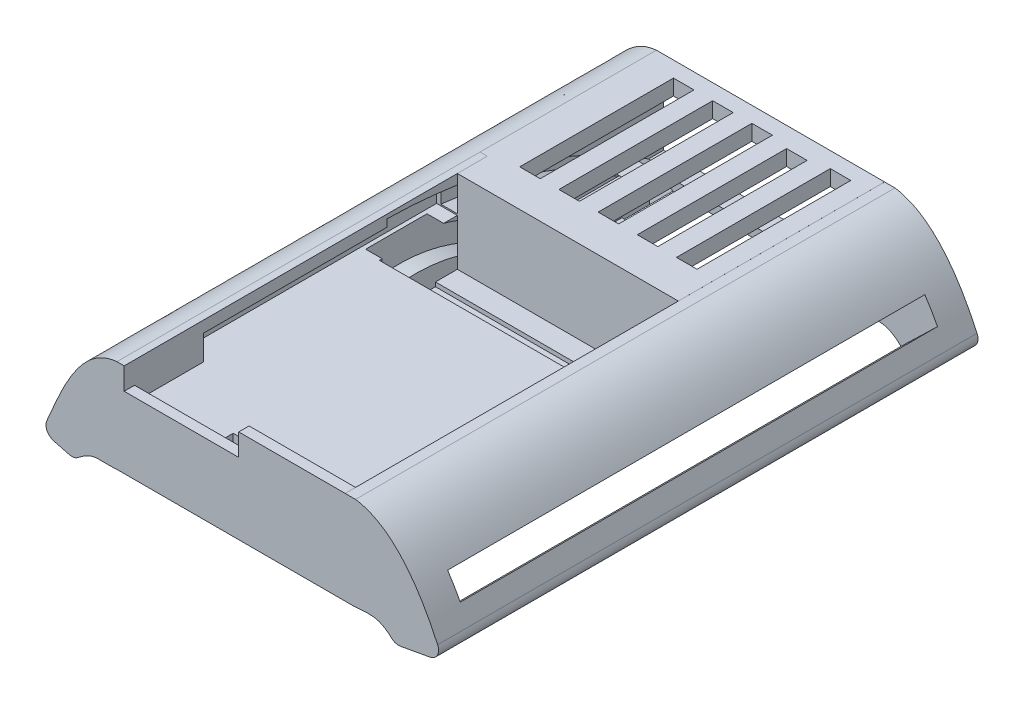
SolidWorks part; units mm, degrees
ref_plane "Front Plane" through (0, 0, 0) normal (0, 0, 1) x (1, 0, 0)
ref_plane "Top Plane" through (0, 0, 0) normal (0, 1, 0) x (1, 0, 0)
ref_plane "Right Plane" through (0, 0, 0) normal (1, 0, 0) x (0, 0, -1)
sketch "Sketch1" plane through (0, 0, 0) normal (0, 0, 1) x (1, 0, 0)
  line L0 (-4.067, -1.1908) -> (-7.2404, -0.3546)
  line L5 (0, 0) -> (22.8691, 0)
  line L9 (23.0423, 8.9983) -> (22.0423, 8.9983)
  line L10 (22.0423, 8.9983) -> (22.0423, 1)
  line L11 (22.0423, 1) -> (0.7423, 1)
  line L12 (0.7423, 1) -> (0.7423, 8.9983)
  line L13 (0.7423, 8.9983) -> (0.0423, 8.9983)
  line L14 (31.4678, -0.3546) -> (26.8755, -1.1908)
  spline S0 degree 3 poles (0.0423, 8.9983) (-4.2131, 8.6488) (-5.9624, 1.8146) (-7.2404, -0.3546) knots 0 0 0 0 1 1 1 1
  spline S1 degree 3 poles (0, 0) (-1.8708, -0.1637) (-2.2399, 0.4307) (-4.067, -1.1908) knots 0 0 0 0 1 1 1 1
  spline S2 degree 2 poles (23.0423, 8.9983) (27.8524, 8.2713) (31.4678, -0.3546) knots 0 0 0 1 1 1
  spline S3 degree 3 poles (22.8691, 0) (24.5642, 0.0744) (25.2973, 0.4291) (26.8755, -1.1908) knots 0 0 0 0 1 1 1 1
  point P13 (0, 0)
  point P14 (0, 0)
  point P15 (22.0587, 5.9972)
  point P16 (0, 0)
  point P17 (0, 0)
  point P18 (0, 0)
  point P19 (26.8687, -1.1908)
  point P20 (31.4678, -0.3546)
  point P21 (0, 0)
  dimension "D3" = 1
  dimension "D1" = 23
  dimension "D2" = 9
  dimension "D4" = 0.7
  dimension "D5" = 1
extrude "Boss-Extrude2" add sketch "Sketch1" along normal blind 52
fillet "Fillet2" radius 1 2 edges at (-4.067, -1.1908, 26) (-7.2404, -0.3546, 26)
ref_plane "Plane10" through (-4.3809, 3.5692, 0) normal (-0.7753, 0.6316, 0) x (0.6316, 0.7753, 0)
sketch "Sketch10" plane through (-4.3809, 3.5692, 0) normal (-0.7753, 0.6316, 0) x (0.6316, 0.7753, 0)
  line L0 (7.0029, 0) -> (-3.689, 0) construction
  line L1 (-3.0069, -50) -> (-0.6561, -50)
  line L2 (-3.0069, -50) -> (-3.0069, -4)
  line L3 (-3.0069, -4) -> (-0.6561, -4)
  line L4 (-0.6561, -50) -> (-0.6561, -4)
  point P4 (-1.8315, -4)
  dimension "D1" = 46
  dimension "D2" = 4
extrude "Cut-Extrude2" cut sketch "Sketch10" against normal blind 6 and the other way blind 3
sketch "Sketch11" plane through (0, 1, 0) normal (0, 1, 0) x (1, 0, 0)
  line L0 (22.0423, 0) -> (0.7423, 0) construction
  line L1 (3.6147, -2) -> (20.6147, -2)
  line L2 (3.6147, -2) -> (3.6147, -17)
  line L3 (3.6147, -17) -> (20.6147, -17)
  line L4 (20.6147, -2) -> (20.6147, -17)
  dimension "D1" = 17
  dimension "D2" = 15
  dimension "D3" = 2
extrude "Peltier" cut sketch "Sketch11" against normal blind 10
sketch "Sketch12" plane through (0, 1, 0) normal (0, 1, 0) x (1, 0, 0)
  line L0 (0.7423, -52) -> (0.7423, 0) construction
  line L1 (0.7423, -22) -> (21.7423, -22)
  line L2 (0.7423, -22) -> (0.7423, -51)
  line L3 (0.7423, -51) -> (21.7423, -51)
  line L4 (21.7423, -22) -> (21.7423, -51)
  line L5 (22.0423, -52) -> (0.7423, -52) construction
  point P4 (21.6862, -25.0592)
  point P5 (0.7604, -25.0044)
  point P6 (1.0987, -24.9782)
  point P7 (2.098, -25.2677)
  point P8 (7.0243, -24.6526)
  point P11 (21.7604, -21.5854)
  dimension "D1" = 29
  dimension "D2" = 21
  dimension "D3" = 1
extrude "Battery" cut sketch "Sketch12" against normal blind 0.4
sketch "Sketch14" plane through (0, 1, 0) normal (0, 1, 0) x (1, 0, 0)
  line L1 (22.0423, -52) -> (0.7423, -52)
  line L2 (22.0423, -52) -> (22.0423, -51)
  line L3 (22.0423, -51) -> (0.7423, -51)
  line L4 (0.7423, -52) -> (0.7423, -51)
extrude "Boss-Extrude4" add sketch "Sketch14" along normal blind 7.9999
sketch "Sketch15" plane through (3.6147, 0, 0) normal (1, 0, 0) x (0, 0, -1)
  line L0 (-2, 1) -> (-17, 1) construction
  line L1 (-17, 0.3705) -> (-13.7023, 0.3705)
  line L2 (-17, 0.3705) -> (-17, 1)
  line L3 (-17, 1) -> (-13.7023, 1)
  line L4 (-13.7023, 0.3705) -> (-13.7023, 1)
  point P7 (0, 0)
  point P8 (-13.7023, 0.3705)
  point P9 (-17, 1)
extrude "Cut-Extrude5" cut sketch "Sketch15" against normal blind 3.6
sketch "Sketch16" plane through (3.6147, 0, 0) normal (1, 0, 0) x (0, 0, -1)
  line L0 (-2, 1) -> (-13.7023, 1) construction
  line L1 (-1.4649, 0.3306) -> (-4.2604, 0.3306)
  line L2 (-1.4649, 0.3306) -> (-1.4649, 1)
  line L3 (-1.4649, 1) -> (-4.2604, 1)
  line L4 (-4.2604, 0.3306) -> (-4.2604, 1)
  point P7 (-4.2604, 0.3306)
extrude "Cut-Extrude6" cut sketch "Sketch16" against normal blind 4.337
fillet "Fillet3" radius 1 2 edges at (3.6147, 0.3306, 3.1302) (3.6147, 0.3705, 15.3511)
sketch "Sketch17" plane through (0.7423, 0, 0) normal (1, 0, 0) x (0, 0, -1)
  line L0 (-26.6799, 8.6073) -> (-26.6799, 5.8973)
  line L1 (-4.2604, 1) -> (-1.4649, 1)
  spline S0 degree 2 poles (-1.4649, 1) (-12.8352, 8.3747) (-26.6799, 8.6073) knots 0 0 0 1 1 1
  spline S1 degree 2 poles (-4.2604, 1) (-14.8676, 6.2725) (-26.6799, 5.8973) knots 0 0 0 1 1 1
  point P5 (0, 0)
  point P8 (0, 0)
  point P9 (-26.6799, 8.6073)
  point P11 (-9.9454, 5.3736)
  point P12 (-17.0967, 4.2862)
  point P13 (-26.6799, 5.8973)
  point P14 (-15.6003, 4.9526)
extrude "Cut-Extrude7" cut sketch "Sketch17" against normal blind 1.6
sketch "Sketch18" plane through (0.7423, 0, 0) normal (1, 0, 0) x (0, 0, -1)
  line L0 (-27.1273, 2.3332) -> (-27.1273, 5.8811)
  line L1 (-17, 1) -> (-13.7023, 1)
  parabola Q0 (-26.6799, 5.8973) -> (-4.2604, 1) focus (-20.1418, -17.3883) apex (-15.3845, 4.9071) construction
  parabola Q1 (-26.6799, 5.8973) -> (-4.2604, 1) focus (-20.1418, -17.3883) apex (-15.3845, 4.9071) construction
  spline S0 degree 2 poles (-13.7023, 1) (-19.5982, 6.7985) (-27.1273, 5.8811) knots 0 0 0 1 1 1
  spline S1 degree 2 poles (-17, 1) (-21.9026, 3.3817) (-27.1273, 2.3332) knots 0 0 0 1 1 1
extrude "Cut-Extrude8" cut sketch "Sketch18" against normal blind 1.6
fillet "Fillet4" radius 1 1 edges at (26.8755, -1.1908, 26)
fillet "Fillet5" radius 1 1 edges at (31.4678, -0.3546, 26)
sketch "Sketch19" plane through (0, 0, 51) normal (0, 0, -1) x (-1, 0, 0)
  line L0 (-0.7423, 0.6) -> (-0.7423, 8.9983) construction
  line L1 (-0.7423, 4.5) -> (-22.0423, 4.5)
  line L2 (-0.7423, 4.5) -> (-0.7423, 5.5)
  line L3 (-0.7423, 5.5) -> (-22.0423, 5.5)
  line L4 (-22.0423, 4.5) -> (-22.0423, 5.5)
  line L5 (-22.0423, 8.9983) -> (-22.0423, 1) construction
  line L6 (-0.7423, 0.6) -> (-21.7423, 0.6) construction
  dimension "D1" = 1
  dimension "D2" = 3.9
extrude "Boss-Extrude5" add sketch "Sketch19" along normal blind 23.6
sketch "Sketch20" plane through (0, 5.5, 0) normal (0, 1, 0) x (1, 0, 0)
  line L0 (0.7423, -51) -> (22.0423, -51) construction
  line L1 (15.7498, -51) -> (8.1239, -51)
  line L2 (15.7498, -51) -> (15.7498, -48.879)
  line L3 (15.7498, -48.879) -> (8.1239, -48.879)
  line L4 (8.1239, -51) -> (8.1239, -48.879)
extrude "Cut-Extrude9" cut sketch "Sketch20" against normal blind 2.6
sketch "Sketch21" plane through (0, 1, 0) normal (0, 1, 0) x (1, 0, 0)
  line L0 (22.0423, -51) -> (22.0423, 0) construction
  line L1 (22.0423, -17) -> (0.7423, -17)
  line L2 (22.0423, -17) -> (22.0423, -19.8861)
  line L3 (22.0423, -19.8861) -> (0.7423, -19.8861)
  line L4 (0.7423, -17) -> (0.7423, -19.8861)
  line L5 (0.7423, -22) -> (0.7423, -17) construction
extrude "Boss-Extrude6" add sketch "Sketch21" along normal blind 8
sketch "Sketch22" plane through (22.0423, 0, 0) normal (-1, 0, 0) x (0, 0, 1)
  line L0 (0, 8.9983) -> (0, 1) construction
  line L1 (17, 9) -> (0, 9)
  line L2 (17, 9) -> (17, 7.5)
  line L3 (17, 7.5) -> (0, 7.5)
  line L4 (0, 9) -> (0, 7.5)
  dimension "D1" = 1.5
extrude "Boss-Extrude7" add sketch "Sketch22" along normal blind 22
sketch "Sketch23" plane through (0.7423, 0, 0) normal (1, 0, 0) x (0, 0, -1)
  line L0 (-27.4, 5.5) -> (-51, 5.5) construction
  line L1 (-44.3676, 5.5) -> (-19.8861, 5.5)
  line L2 (-44.3676, 5.5) -> (-44.3676, 7.9035)
  line L3 (-44.3676, 7.9035) -> (-19.8861, 7.9035)
  line L4 (-19.8861, 5.5) -> (-19.8861, 7.9035)
  line L5 (-19.8861, 8.9983) -> (-19.8861, 8.0406) construction
extrude "Cut-Extrude10" cut sketch "Sketch23" against normal blind 2
sketch "Sketch24" plane through (20.6147, 0, 0) normal (-1, 0, 0) x (0, 0, 1)
  line L0 (17, 0) -> (17, 1) construction
  line L1 (2, 0) -> (17, 0)
  line L2 (2, 0) -> (2, 0.2114)
  line L3 (2, 0.2114) -> (17, 0.2114)
  line L4 (17, 0) -> (17, 0.2114)
extrude "Boss-Extrude8" add sketch "Sketch24" along normal blind 2
sketch "Sketch25" plane through (3.6147, 0, 0) normal (1, 0, 0) x (0, 0, -1)
  line L0 (-4.2604, 0) -> (-13.7023, 0) construction
  line L1 (-6.8876, 0) -> (-11.6748, 0)
  line L2 (-6.8876, 0) -> (-6.8876, 0.2374)
  line L3 (-6.8876, 0.2374) -> (-11.6748, 0.2374)
  line L4 (-11.6748, 0) -> (-11.6748, 0.2374)
extrude "Boss-Extrude9" add sketch "Sketch25" along normal blind 2
sketch "Sketch26" plane through (0, 0, 51) normal (0, 0, -1) x (-1, 0, 0)
  line L0 (-0.7423, 5.5) -> (-0.7423, 8.9983) construction
  line L1 (-0.7423, 6.8737) -> (-11.7785, 6.8737)
  line L2 (-0.7423, 6.8737) -> (-0.7423, 8.9999)
  line L3 (-0.7423, 8.9999) -> (-11.7785, 8.9999)
  line L4 (-11.7785, 6.8737) -> (-11.7785, 8.9999)
  line L5 (-22.0423, 8.9999) -> (-0.7423, 8.9999) construction
extrude "Cut-Extrude11" cut sketch "Sketch26" against normal blind 2
ref_plane "Plane7" through (1.1804, 5.0597, 0) normal (0.2272, 0.9739, 0) x (0.9739, -0.2272, 0)
ref_plane "Plane8" through (16.4013, 15.8642, 0) normal (0.7188, 0.6952, 0) x (0, 0, -1)
sketch "Sketch27" plane through (16.4013, 15.8642, 0) normal (0.7188, 0.6952, 0) x (0, 0, -1)
  line L0 (0, -19.0571) -> (0, -15.8995) construction
  line L1 (-3, -16.8482) -> (-49, -16.8482)
  line L2 (-3, -16.8482) -> (-3, -19.1782)
  line L3 (-3, -19.1782) -> (-49, -19.1782)
  line L4 (-49, -16.8482) -> (-49, -19.1782)
  point P6 (-3, -15.6717)
  point P7 (-3, -18.8293)
  point P8 (-3, -19.1782)
  dimension "D1" = 46
  dimension "D2" = 3
  dimension "D3" = 2.33
extrude "Cut-Extrude12" cut sketch "Sketch27" against normal blind 11 and the other way blind 2
sketch "Sketch28" plane through (0, 9, 0) normal (0, 1, 0) x (1, 0, 0)
  line L1 (20.2889, -1.507) -> (18.3099, -1.507)
  line L2 (20.2889, -1.507) -> (20.2889, -16.3291)
  line L3 (20.2889, -16.3291) -> (18.3099, -16.3291)
  line L4 (18.3099, -1.507) -> (18.3099, -16.3291)
  line L5 (16.5099, -16.3291) -> (14.5309, -16.3291)
  line L6 (16.5099, -16.3291) -> (16.5099, -1.9398)
  line L7 (16.5099, -1.9398) -> (14.5309, -1.9398)
  line L8 (14.5309, -16.3291) -> (14.5309, -1.9398)
  line L9 (12.7309, -1.507) -> (10.752, -1.507)
  line L10 (12.7309, -1.507) -> (12.7309, -16.3291)
  line L11 (12.7309, -16.3291) -> (10.752, -16.3291)
  line L12 (10.752, -1.507) -> (10.752, -16.3291)
  line L13 (8.952, -16.3291) -> (6.973, -16.3291)
  line L14 (8.952, -16.3291) -> (8.952, -1.507)
  line L15 (8.952, -1.507) -> (6.973, -1.507)
  line L16 (6.973, -16.3291) -> (6.973, -1.507)
  line L17 (5.173, -1.507) -> (3.194, -1.507)
  line L18 (5.173, -1.507) -> (5.173, -16.3291)
  line L19 (5.173, -16.3291) -> (3.194, -16.3291)
  line L20 (3.194, -1.507) -> (3.194, -16.3291)
  point P20 (14.5277, -16.7467)
  point P21 (0, 0)
  dimension "D1" = 1.8
  dimension "D2" = 1.8
  dimension "D3" = 1.8
  dimension "D4" = 1.8
extrude "Cut-Extrude13" cut sketch "Sketch28" against normal blind 3
